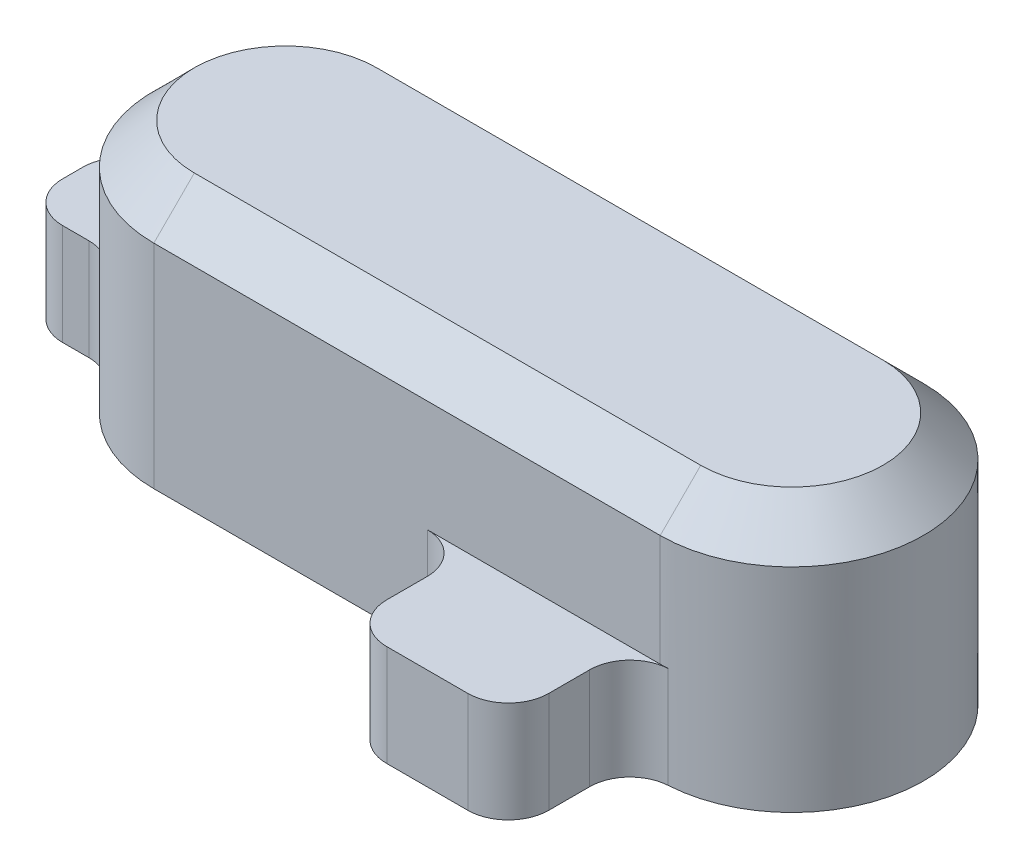
SolidWorks part; units mm, degrees
ref_plane "Plane XZ" through (0, 0, 0) normal (0, 0, 1) x (1, 0, 0)
ref_plane "Plane XY" through (0, 0, 0) normal (0, 1, 0) x (1, 0, 0)
ref_plane "Plane YZ" through (0, 0, 0) normal (1, 0, 0) x (0, 0, -1)
sketch "Sketch1" plane through (0, 0, 0) normal (0, 1, 0) x (1, 0, 0)
  line L0 (-3.175, 0) -> (3.175, 0) construction
  line L1 (-3.175, 1.905) -> (3.175, 1.905) construction
  line L2 (-3.175, -1.905) -> (3.175, -1.905) construction
  line L3 (-3.175, 1.651) -> (3.175, 1.651)
  line L4 (-3.175, -1.651) -> (3.175, -1.651)
  arc A0 (-3.175, 1.905) -> (-3.175, -1.905) centre (-3.175, 0) ccw construction
  arc A1 (3.175, -1.905) -> (3.175, 1.905) centre (3.175, 0) ccw construction
  arc A2 (3.175, -1.651) -> (3.175, 1.651) centre (3.175, 0) ccw
  arc A3 (-3.175, 1.651) -> (-3.175, -1.651) centre (-3.175, 0) ccw
  point P2 (0, 0)
  dimension "D1" = 1.905
  dimension "D2" = 6.35
  dimension "D3" = 0.254
extrude "Boss-Extrude1" add sketch "Sketch1" along normal blind 3.175
sketch "Sketch2" plane through (0, 0, 0) normal (0, -1, 0) x (1, 0, 0)
  line L0 (-3.175, 1.651) -> (3.175, 1.651) construction
  line L1 (0.762, 1.651) -> (2.794, 1.651)
  line L2 (0.762, 1.651) -> (0.762, 3.175)
  line L3 (0.762, 3.175) -> (2.794, 3.175)
  line L4 (2.794, 1.651) -> (2.794, 3.175)
  line L5 (-3.81, 0) -> (0, 0) construction
  line L6 (-3.81, 0.635) -> (-5.842, 0.635)
  line L7 (-3.81, 0.635) -> (-3.81, -0.635)
  line L8 (-3.81, -0.635) -> (-5.842, -0.635)
  line L9 (-5.842, 0.635) -> (-5.842, -0.635)
  line L10 (1.778, 3.175) -> (1.778, 1.651) construction
  dimension "D1" = 5.842
  dimension "D2" = 1.27
  dimension "D3" = 2.032
  dimension "D4" = 3.175
  dimension "D5" = 0.762
  dimension "D6" = 2.032
extrude "Boss-Extrude2" add sketch "Sketch2" against normal blind 1.27
chamfer "Chamfer1" distance 0.508 angle 45 4 edges at (0, 3.175, 1.651) (4.826, 3.175, 0) (-4.826, 3.175, 0) (0, 3.175, -1.651)
sketch "Sketch3" plane through (0, 3.175, 0) normal (0, 1, 0) x (1, 0, 0)
  line L0 (3.175, 1.143) -> (-3.175, 1.143) construction
  line L1 (-3.1532, 1.016) -> (3.1532, 1.016) construction
  line L2 (-3.1532, 1.016) -> (-3.1532, -1.016) construction
  line L3 (-3.1532, -1.016) -> (3.1532, -1.016) construction
  line L4 (3.1532, 1.016) -> (3.1532, -1.016) construction
  line L6 (0, 1.016) -> (0, -1.016) construction
  text T0 "1" font "Calibri" height 2.032
  dimension "D1" = 0.127
  dimension "D3" = 2.032
fillet "Fillet1" radius 0.508 8 edges at (0.762, 0.635, 3.175) (2.794, 0.635, 3.175) (2.794, 0.635, 1.651) (0.762, 0.635, 1.651) (-5.842, 0.635, 0.635) (-5.842, 0.635, -0.635) (-4.699, 0.635, -0.635) (-4.699, 0.635, 0.635)
